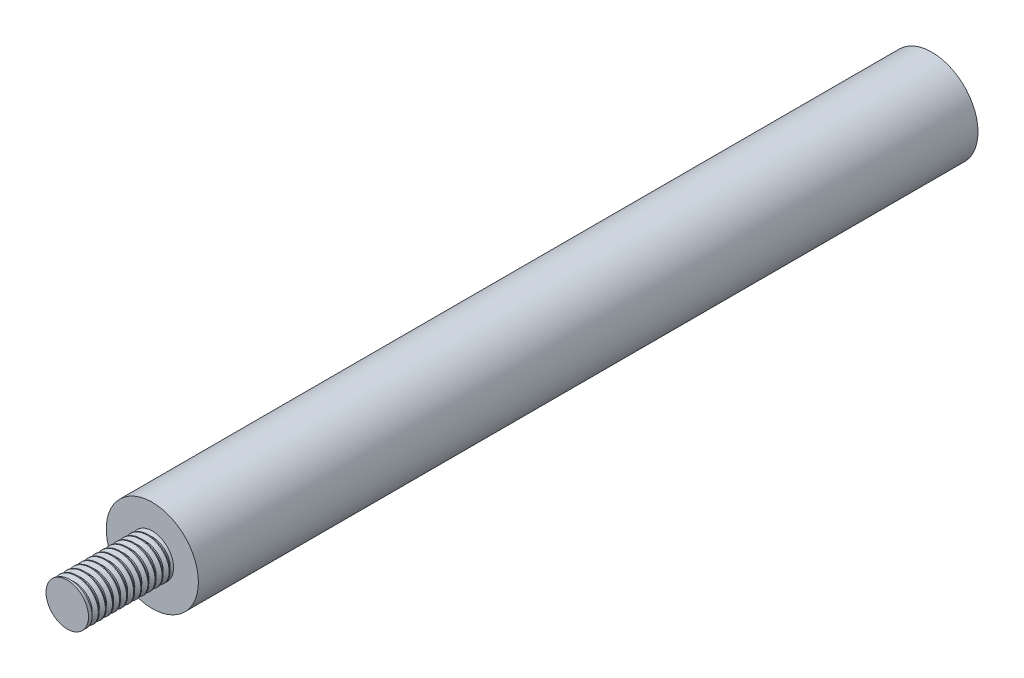
SolidWorks part; units mm, degrees
ref_plane "Front Plane" through (0, 0, 0) normal (0, 0, 1) x (1, 0, 0)
ref_plane "Top Plane" through (0, 0, 0) normal (0, 1, 0) x (1, 0, 0)
ref_plane "Right Plane" through (0, 0, 0) normal (1, 0, 0) x (0, 0, -1)
sketch "Sketch1" plane through (0, 0, 0) normal (0, 0, 1) x (1, 0, 0)
  circle A0 centre (0, 0) radius 3
  circle A1 centre (0, 0) radius 6.5
  dimension "D1" = 13
  dimension "D2" = 6
extrude "Boss-Extrude1" add sketch "Sketch1" along normal blind 122 contours A0 region at (0, 0, 0)
extrude "Boss-Extrude2" add sketch "Sketch1<3>" along normal blind 110
sketch "Sketch1<3>" plane through (0, 0, 0) normal (0, 0, 1) x (1, 0, 0) same geometry as "Sketch1"
thread "Thread1" pitch 1 method cut profile "Thread Profile1" start angle 0, offset 0, length 12, pitch 1, diameter 6
ref_plane "Plane1" through (-3, 0, 122) normal (0, -1, 0) x (-1, 0, 0)
sketch "Thread Profile1" plane through (-3, 0, 122) normal (0, -1, 0) x (-1, 0, 0)
  line L0 (0, 0) -> (0, 1) construction
  line L11 (0, 0) -> (0, 0.875)
  line L12 (0, 0.875) -> (-0.5413, 0.5625)
  line L13 (-0.5413, 0.5625) -> (-0.5413, 0.3125)
  line L15 (-0.5413, 0.3125) -> (0, 0)
  line L17 (-0.5413, 0.4375) -> (0, 0.4375) construction
  point P2 (0, 0)
  dimension "Pitch" = 1
  dimension "Profile_Angle" = 60
  dimension "Profile_Land" = 0.25
  dimension "Profile_Height" = 0.5413
sketch "Sketch4" plane through (0, 0, 0) normal (0, 0, -1) x (-1, 0, 0)
  circle A0 centre (0, 0) radius 3
  dimension "D1" = 6
extrude "Cut-Extrude1" cut sketch "Sketch4" against normal blind 10
